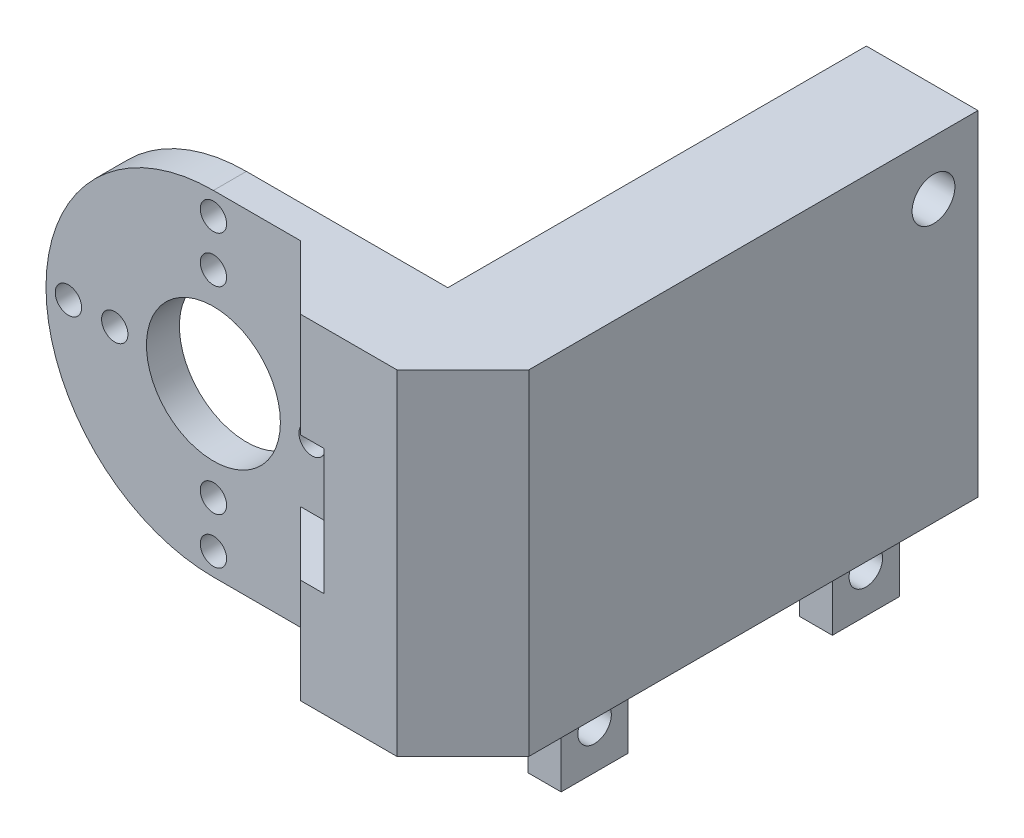
SolidWorks part; units mm, degrees
ref_plane "Front Plane" through (0, 0, 0) normal (0, 0, 1) x (1, 0, 0)
ref_plane "Top Plane" through (0, 0, 0) normal (0, 1, 0) x (1, 0, 0)
ref_plane "Right Plane" through (0, 0, 0) normal (1, 0, 0) x (0, 0, -1)
sketch "Sketch1" plane through (0, 0, 0) normal (0, 0, 1) x (1, 0, 0)
  circle A0 centre (0, 0) radius 25.4
  circle A1 centre (0, 0) radius 10.16
  circle A4 centre (0, -22) radius 2
  circle A5 centre (0, -14.9689) radius 2
  circle A6 centre (-14.9689, 0) radius 2
  circle A7 centre (-22, 0) radius 2
  circle A8 centre (0, 14.9689) radius 2
  circle A9 centre (0, 22) radius 2
  circle A10 centre (14.9689, 0) radius 2
  circle A11 centre (22, 0) radius 2
  point P23 (0, 0)
  dimension "D1" = 50.8
  dimension "D2" = 20.32
  dimension "D7" = 4
  dimension "D5" = 4
  dimension "D3" = 4
  dimension "D4" = 22
  dimension "D6" = 14.9689
extrude "Boss-Extrude1" add sketch "Sketch1" along normal blind 5
sketch "Sketch2" plane through (0, 0, 5) normal (0, 0, 1) x (1, 0, 0)
  line L0 (0, 25.4) -> (5.0687, 21.4037)
  line L1 (0, 25.4) -> (35.56, 25.4)
  line L3 (0, -25.4) -> (35.56, -25.4)
  line L4 (35.56, 25.4) -> (35.56, -25.4)
  line L5 (5.0687, 21.4037) -> (24.1594, 2.0379)
  line L6 (24.1594, 2.0379) -> (24.1594, -2.8586)
  line L7 (24.1594, -2.8586) -> (0, -25.4)
  circle A0 centre (0, 0) radius 25.4 construction
  circle A1 centre (0, 0) radius 25.4 construction
  dimension "D1" = 50.8
  dimension "D2" = 35.56
extrude "Boss-Extrude2" add sketch "Sketch2" against normal up to surface (5 mm away) up to face at (25.4, 0, 0)
sketch "Sketch3" plane through (0, 0, 0) normal (0, 0, -1) x (-1, 0, 0)
  line L0 (-35.56, -25.4) -> (0, -25.4) construction
  line L1 (-35.56, 25.4) -> (-30.56, 25.4)
  line L2 (-35.56, 25.4) -> (-35.56, -25.4)
  line L3 (-35.56, -25.4) -> (-30.56, -25.4)
  line L4 (-30.56, 25.4) -> (-30.56, -25.4)
  dimension "D1" = 5
extrude "Boss-Extrude3" add sketch "Sketch3" along normal blind 63.5
sketch "Sketch4" plane through (30.56, 0, 0) normal (-1, 0, 0) x (0, 0, 1)
  line L0 (-63.5, 25.4) -> (0, 25.4) construction
  line L1 (-63.5, 25.4) -> (-53.34, 25.4)
  line L2 (-63.5, 25.4) -> (-63.5, 44.45)
  line L3 (-63.5, 44.45) -> (-53.34, 44.45)
  line L4 (-53.34, 25.4) -> (-53.34, 44.45)
  line L5 (-22.352, 25.4) -> (-12.192, 25.4)
  line L6 (-22.352, 25.4) -> (-22.352, 44.45)
  line L7 (-22.352, 44.45) -> (-12.192, 44.45)
  line L8 (-12.192, 25.4) -> (-12.192, 44.45)
  circle A0 centre (-58.42, 38.1) radius 2.54
  circle A1 centre (-17.272, 38.1) radius 2.54
  dimension "D4" = 5.08
  dimension "D5" = 5.08
  dimension "D6" = 5.08
  dimension "D7" = 5.08
  dimension "D8" = 6.35
  dimension "D9" = 6.35
  dimension "D1" = 10.16
  dimension "D2" = 10.16
  dimension "D3" = 30.988
  dimension "D10" = 19.05
  dimension "D11" = 19.05
extrude "Boss-Extrude4" add sketch "Sketch4" against normal up to surface (5 mm away) up to face at (35.56, 0, -29.25)
sketch "Sketch5" plane through (35.56, 0, 0) normal (1, 0, 0) x (0, 0, -1)
  line L1 (-5, 25.4) -> (63.5, 25.4)
  line L2 (-5, 25.4) -> (-5, -25.4)
  line L3 (-5, -25.4) -> (63.5, -25.4)
  line L4 (63.5, 25.4) -> (63.5, -25.4)
extrude "Boss-Extrude5" add sketch "Sketch5" along normal blind 11.938
ref_plane "Plane1" through (0, 0, -29.25) normal (0, 0, 1) x (1, 0, 0)
mirror "Mirror5" about plane through (0, 0, 0) normal (0, 1, 0) of "Boss-Extrude4"
sketch "Sketch8" plane through (30.56, 0, 0) normal (-1, 0, 0) x (0, 0, 1)
  line L1 (0, 25.4) -> (-85.9509, 25.4)
  line L2 (0, 25.4) -> (0, 69.0926)
  line L3 (0, 69.0926) -> (-85.9509, 69.0926)
  line L4 (-85.9509, 25.4) -> (-85.9509, 69.0926)
extrude "Cut-Extrude2" cut sketch "Sketch8" against normal blind 9
sketch "Sketch10" plane through (0, 0, 0) normal (0, 0, -1) x (-1, 0, 0)
  circle A0 centre (0, 0) radius 32.5
  dimension "D1" = 65
extrude "Cut-Extrude3" cut sketch "Sketch10" along normal blind 78.088
sketch "Sketch11" plane through (30.56, 0, 0) normal (-1, 0, 0) x (0, 0, 1)
  line L0 (-63.5, 11.0606) -> (-63.5, -11.0606) construction
  line L1 (-63.5, 25.4) -> (0, 25.4) construction
  circle A0 centre (-56.75, 17.15) radius 3.25
  dimension "D1" = 6.5
  dimension "D2" = 6.75
  dimension "D3" = 8.25
extrude "Cut-Extrude4" cut sketch "Sketch11" against normal through all
sketch "Sketch12" plane through (30.56, 0, 0) normal (-1, 0, 0) x (0, 0, 1)
  line L0 (0, 11.0606) -> (-54, 11.0606)
  dimension "D1" = 54
sketch "Sketch13" plane through (30.56, 0, 0) normal (-1, 0, 0) x (0, 0, 1)
  line L1 (-63.2741, 17.15) -> (-60.012, 11.5)
  line L2 (-60.012, 11.5) -> (-53.488, 11.5)
  line L3 (-53.488, 11.5) -> (-50.2259, 17.15)
  line L4 (-50.2259, 17.15) -> (-53.488, 22.8)
  line L5 (-53.488, 22.8) -> (-60.012, 22.8)
  line L6 (-60.012, 22.8) -> (-63.2741, 17.15)
  circle A0 centre (-56.75, 17.15) radius 5.65 construction
  circle A1 centre (-56.75, 17.15) radius 3.25 construction
  circle A2 centre (-56.75, 17.15) radius 3.25
  dimension "D1" = 11.3
  dimension "D2" = 0
  dimension "D3" = 0
extrude "Cut-Extrude5" cut sketch "Sketch13" against normal blind 7.7
sketch "Sketch14" plane through (0, 0, 5) normal (0, 0, 1) x (1, 0, 0)
  line L0 (0, -25.4) -> (47.498, -25.4) construction
  line L1 (47.498, 25.4) -> (26.4173, 25.4)
  line L2 (47.498, 25.4) -> (47.498, -25.4)
  line L3 (47.498, -25.4) -> (26.4173, -25.4)
  line L4 (26.4173, 25.4) -> (26.4173, -25.4)
  line L5 (37.675, 0) -> (-37.675, 0) construction
  line L6 (26.4173, 25.4) -> (12.8408, 25.4)
  line L7 (26.4173, 25.4) -> (26.4173, 9.5397)
  line L8 (26.4173, 9.5397) -> (12.8408, 9.5397)
  line L9 (12.8408, 25.4) -> (12.8408, 9.5397)
  line L10 (26.4173, -9.5397) -> (12.8408, -9.5397)
  line L11 (12.8408, -25.4) -> (12.8408, -9.5397)
  line L12 (26.4173, -25.4) -> (12.8408, -25.4)
  line L13 (26.4173, -25.4) -> (26.4173, -9.5397)
  line M2 (0, -25.4) -> (47.498, -25.4)
  line M3 (47.498, -25.4) -> (47.498, 25.4)
  line M4 (47.498, 25.4) -> (0, 25.4)
extrude "Boss-Extrude6" add sketch "Sketch14" along normal blind 9.652 contours L9 L8 L4 M4 | L4 M4 M2 M3 | L11 L4 L10 M2 region at (36.9576, 0, 5) region at (19.629, 17.4699, 5) region at (19.629, -17.4699, 5)
chamfer "Chamfer1" distance 10 angle 45 3 edges at (47.498, 0, 14.652) (12.8408, -17.4699, 14.652) (12.8408, 17.4699, 14.652)
